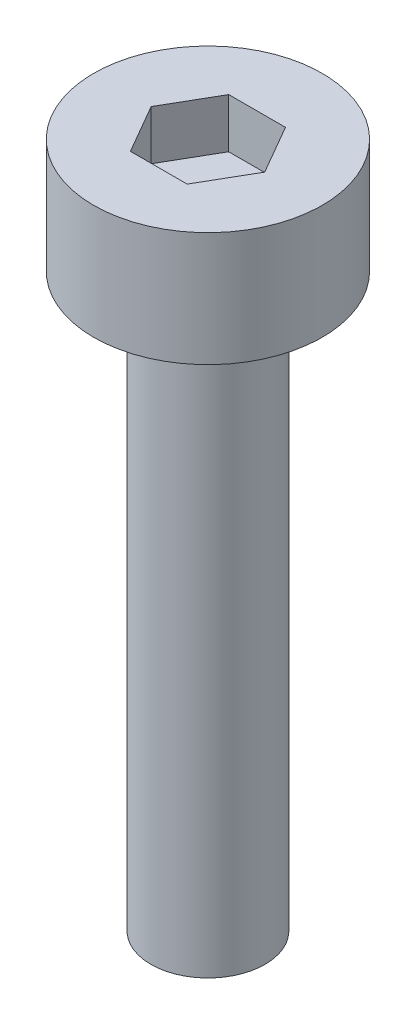
SolidWorks part; units mm, degrees
ref_plane "Front Plane" through (0, 0, 0) normal (0, 0, 1) x (1, 0, 0)
ref_plane "Top Plane" through (0, 0, 0) normal (0, 1, 0) x (1, 0, 0)
ref_plane "Right Plane" through (0, 0, 0) normal (1, 0, 0) x (0, 0, -1)
sketch "Sketch1" plane through (0, 0, 0) normal (0, 1, 0) x (1, 0, 0)
  circle A0 centre (0, 0) radius 1.5
  dimension "D1" = 3
extrude "ScrewShaft" add sketch "Sketch1" along normal blind 15
sketch "Sketch2" plane through (0, 15, 0) normal (0, 1, 0) x (1, 0, 0)
  circle A0 centre (0, 0) radius 3
  dimension "D1" = 6
extrude "Boss-Extrude2" add sketch "Sketch2" along normal blind 3
sketch "Sketch3" plane through (0, 18, 0) normal (0, 1, 0) x (1, 0, 0)
  line L0 (0, 0) -> (0, 1.29) construction
  line L1 (1.4896, 0) -> (0.7448, 1.29)
  line L2 (0.7448, 1.29) -> (-0.7448, 1.29)
  line L3 (-0.7448, 1.29) -> (-1.4896, 0)
  line L4 (-1.4896, 0) -> (-0.7448, -1.29)
  line L5 (-0.7448, -1.29) -> (0.7448, -1.29)
  line L6 (0.7448, -1.29) -> (1.4896, 0)
  circle A0 centre (0, 0) radius 1.29 construction
  dimension "D1" = 2.58
extrude "Cut-Extrude1" cut sketch "Sketch3" against normal blind 1.3
equation "\"X-ROD-SPACING\"=45"
equation "\"Y-ROD-SPACING\"=75"
equation "\"Z-ROD-SPACING\"=17.5"
equation "\"Y-BED-OFFSET\"=2"
equation "\"Y-BED-ROD-INSET\"=3.5"
equation "\"T-SLOT-NUT-FILLET-RADIUS\"=0.5"
equation "\"T-SLOT-SCREW-SHAFT-RADIUS\"=1.55"
equation "\"T-SLOT-SCREW-SHAFT-CUTOUT-LENGTH\"=11"
equation "\"T-SLOT-NUT-DEPTH\"=3.5"
equation "\"T-SLOT-NUT-WIDTH\"=2.85"
equation "\"T-SLOT-NUT-END-DISTANCE\"=8"
equation "\"ACRYLIC-THICKNESS\"=10"
equation "\"ACRYLIC-THICKNESS2\"=4.5"
equation "\"ACRYLIC-TAB-CUTOUT-SIZE\"=\"ACRYLIC-THICKNESS\"+\"ACRYLIC-TAB-TOLERANCE\"*2"
equation "\"ACRYLIC-TAB-WIDTH\"=\"ACRYLIC-THICKNESS\""
equation "\"ACRYLIC-M3-HOLE\"=2.9"
equation "\"SMOOTHROD-CAP-SCREW-DISTANCE\"=20"
equation "\"FRAME-WIDTH-INNER\"=370"
equation "\"NEMA17-HOLE-SPACING\"=31"
equation "\"NEMA17-CENTRAL-CUTOUT\"=22.5"
equation "\"Z-BRACKET-REACH\"=57"
equation "\"TOP-BRACKET-SPACING\"=40"
equation "\"SMOOTHROD-X-LENGTH\"=350"
equation "\"SMOOTHROD-Y-LENGTH\"=350"
equation "\"SMOOTHROD-Z-LENGTH\"=350"
equation "\"SMOOTHROD-TIGHTENING-HEADROOM\"=.25"
equation "\"LEADSCREW-Z-LENGTH\"=300"
equation "\"SCREW-LENGTH-FRAME\"=\"ACRYLIC-THICKNESS\" + 10"
equation "\"SCREW-HEAD-RADIUS\"=6"
equation "\"PRINTED-X-SMOOTHROD-DIAMETER\"=8.8"
equation "\"PRINTED-X-SMOOTHROD-CUTOUT\"=10"
equation "\"PRINTED-X-BASE-HEIGHT\"=10"
equation "\"PRINTED-LM8UU-CUTOUT-SIZE\"=15.5"
equation "\"PRINTED-LM8UU-CUTOUT-LENGTH\"=24.5"
equation "\"PRINTED-X-IDLER-HEIGHT\"=16"
equation "\"PSU-MOUNTING-WIDTH\"=95"
equation "\"PSU-MOUNTING-HEIGHT\"=177"
equation "\"D1@ScrewShaft\"=\"SCREW-LENGTH-MOTOR\""
equation "\"D1@Sketch2\"=\"SCREW-HEAD-RADIUS\""
equation "\"Y-BED-SCREW-SPACING\"=209"
equation "\"Y-BED-SCREW-CUTOUT-SLOT-HEIGHT\"=2"
equation "\"Z-ROD-INSET\"=13.5"
equation "\"SCREW-LENGTH-MOTOR\"=\"ACRYLIC-THICKNESS\" + 5"
equation "\"Y-BELT-TO-ROD-DISTANCE\"=20"
equation "\"SPOOL-HOLDER-ROD-SPACING\"=150"
